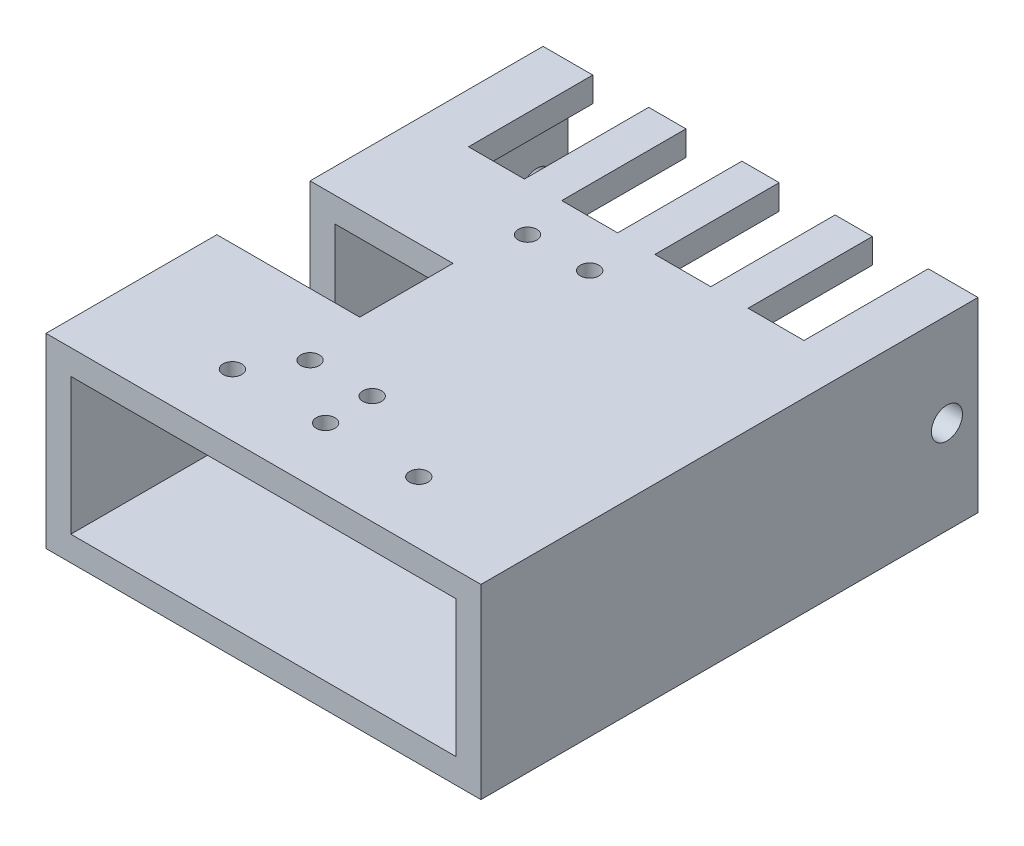
SolidWorks part; units mm, degrees
ref_plane "Front Plane" through (0, 0, 0) normal (0, 0, 1) x (1, 0, 0)
ref_plane "Top Plane" through (0, 0, 0) normal (0, 1, 0) x (1, 0, 0)
ref_plane "Right Plane" through (0, 0, 0) normal (1, 0, 0) x (0, 0, -1)
sketch "Sketch1" plane through (0, 0, 0) normal (0, 1, 0) x (1, 0, 0)
  line L1 (0, 0) -> (88.9, 0)
  line L2 (0, 0) -> (0, 101.6)
  line L3 (0, 101.6) -> (88.9, 101.6)
  line L4 (88.9, 0) -> (88.9, 101.6)
  dimension "D1" = 101.6
  dimension "D2" = 88.9
extrude "Boss-Extrude1" add sketch "Sketch1" along normal blind 38.1 contours L1 L4 L3 L2
shell "Shell1" thickness 5.08 removed face at (44.45, 19.05, -101.6) removed face at (44.45, 19.05, 0)
sketch "Sketch4" plane through (0, 0, 0) normal (0, -1, 0) x (1, 0, 0)
  line L0 (0, 0) -> (0, -101.6) construction
  line L1 (0, -34.925) -> (29.21, -34.925)
  line L2 (0, -34.925) -> (0, -53.975)
  line L3 (0, -53.975) -> (29.21, -53.975)
  line L4 (29.21, -34.925) -> (29.21, -53.975)
  line L6 (0, -101.6) -> (88.9, -101.6) construction
  point P8 (29.21, -44.45)
  dimension "D1" = 19.05
  dimension "D2" = 29.21
  dimension "D3" = 57.15
extrude "Cut-Extrude3" cut sketch "Sketch4" against normal through all from offset 19.05 offset against normal yes
sketch "Sketch5" plane through (0, 38.1, 0) normal (0, 1, 0) x (1, 0, 0)
  line L0 (0, 101.6) -> (88.9, 101.6) construction
  line L1 (10.16, 101.6) -> (21.59, 101.6)
  line L2 (10.16, 101.6) -> (10.16, 76.2)
  line L3 (10.16, 76.2) -> (21.59, 76.2)
  line L4 (21.59, 101.6) -> (21.59, 76.2)
  line L5 (29.21, 101.6) -> (29.21, 76.2)
  line L6 (29.21, 101.6) -> (40.64, 101.6)
  line L7 (40.64, 101.6) -> (40.64, 76.2)
  line L8 (29.21, 76.2) -> (40.64, 76.2)
  line L9 (48.26, 101.6) -> (48.26, 76.2)
  line L10 (48.26, 101.6) -> (59.69, 101.6)
  line L11 (59.69, 101.6) -> (59.69, 76.2)
  line L12 (48.26, 76.2) -> (59.69, 76.2)
  line L13 (67.31, 101.6) -> (67.31, 76.2)
  line L14 (67.31, 101.6) -> (78.74, 101.6)
  line L15 (78.74, 101.6) -> (78.74, 76.2)
  line L16 (67.31, 76.2) -> (78.74, 76.2)
  line L17 (10.16, 88.9) -> (78.74, 88.9) construction
  line L19 (10.16, 101.6) -> (5.08, 101.6) construction
  line L20 (0, 53.975) -> (0, 101.6) construction
  line L21 (78.74, 101.6) -> (83.82, 101.6) construction
  line L22 (88.9, 0) -> (88.9, 101.6) construction
  point P20 (15.875, 76.2)
  point P23 (34.925, 76.2)
  dimension "D1" = 25.4
  dimension "D2" = 11.43
  dimension "D4" = 5.08
  dimension "D5" = 5.08
  dimension "D6" = 19.05
  dimension "D3" = 4
extrude "Cut-Extrude4" cut sketch "Sketch5" against normal through all
sketch "Sketch6" plane through (0, 0, 0) normal (-1, 0, 0) x (0, 0, 1)
  line L0 (-101.6, 38.1) -> (-101.6, 0) construction
  circle A0 centre (-95.25, 19.05) radius 3.175
  point P6 (-101.6, 19.05)
  dimension "D1" = 6.35
  dimension "0.25" = 6.35
extrude "Cut-Extrude5" cut sketch "Sketch6" against normal through all and the other way blind 4.2672
sketch "Sketch7" plane through (0, 38.1, 0) normal (0, 1, 0) x (1, 0, 0)
  line L0 (0, 0) -> (88.9, 0) construction
  line L1 (48.26, 76.2) -> (59.69, 76.2) construction
  line L2 (25.4, 12.7) -> (63.5, 12.7) construction
  line L3 (0, 0) -> (0, 34.925) construction
  line L4 (29.21, 44.45) -> (38.1, 44.45) construction
  line L5 (29.21, 53.975) -> (29.21, 34.925) construction
  line L6 (38.1, 66.675) -> (38.1, 22.225) construction
  circle A0 centre (44.45, 12.7) radius 1.905
  circle A2 centre (25.4, 12.7) radius 1.905
  circle A3 centre (63.5, 12.7) radius 1.905
  circle A6 centre (31.75, 66.675) radius 1.905
  circle A7 centre (44.45, 66.675) radius 1.905
  circle A8 centre (44.45, 22.225) radius 1.905
  circle A9 centre (31.75, 22.225) radius 1.905
  point P4 (44.45, 0)
  point P17 (38.1, 44.45)
  dimension "D1" = 3.81
  dimension "D6" = 3.81
  dimension "D2" = 63.5
  dimension "D3" = 19.05
  dimension "D4" = 38.1
  dimension "D5" = 44.45
  dimension "D7" = 6.35
extrude "Cut-Extrude6" cut sketch "Sketch7" against normal up to next
sketch "Sketch9" plane through (0, 0, 0) normal (-1, 0, 0) x (0, 0, 1)
  line L0 (0, 0) -> (-101.6, 0) construction
  line L1 (-39.37, 0) -> (-29.21, 0)
  line L2 (-39.37, 0) -> (-39.37, 6.35)
  line L3 (-39.37, 6.35) -> (-29.21, 6.35)
  line L4 (-29.21, 0) -> (-29.21, 6.35)
  line L5 (-44.45, 19.05) -> (-44.45, 0) construction
  line L6 (-34.925, 19.05) -> (-53.975, 19.05) construction
  line L8 (-49.53, 6.35) -> (-59.69, 6.35)
  line L9 (-59.69, 0) -> (-59.69, 6.35)
  line L10 (-49.53, 0) -> (-59.69, 0)
  line L11 (-49.53, 0) -> (-49.53, 6.35)
  dimension "D1" = 10.16
  dimension "D2" = 10.16
  dimension "D3" = 6.35
extrude "Boss-Extrude2" add sketch "Sketch9" along normal blind 6.35
sketch "Sketch10" plane through (0, 0, -29.21) normal (0, 0, 1) x (1, 0, 0)
  line L0 (-6.35, 0) -> (-6.35, 6.35) construction
  line L1 (-6.35, 6.35) -> (0, 6.35) construction
  line L2 (-6.35, 0) -> (0, 0) construction
  line L3 (-3.175, 7.6651) -> (-3.175, 6.35)
  line L4 (-3.175, 0) -> (-3.175, -1.3151)
  arc A0 (-3.175, 6.35) -> (-3.175, 0) centre (-3.175, 3.175) ccw
  arc A1 (-3.175, 7.6651) -> (-3.175, -1.3151) centre (-3.175, 3.175) ccw
  circle A2 centre (-3.175, 3.175) radius 2.3813
  dimension "D1" = 4.7625
extrude "Cut-Extrude7" cut sketch "Sketch10" against normal up to surface (30.48 mm away) up to face at (-3.175, 3.175, -59.69)
